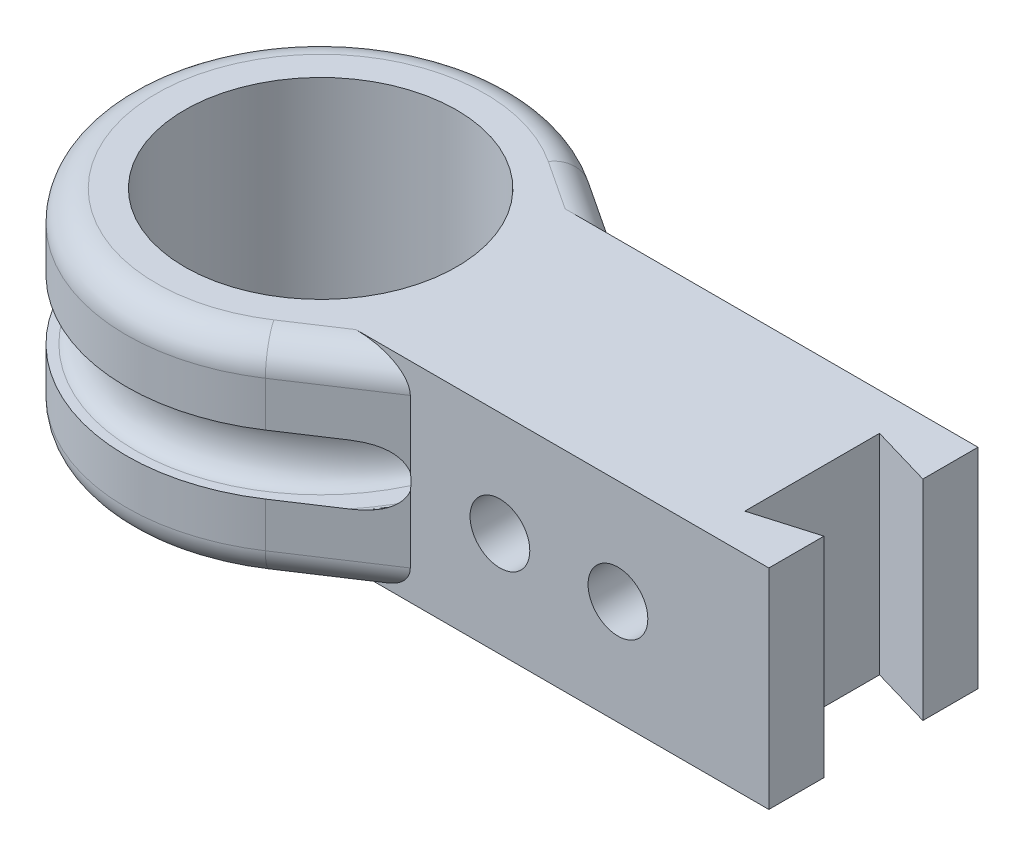
SolidWorks part; units mm, degrees
ref_plane "Front Plane" through (0, 0, 0) normal (0, 0, 1) x (1, 0, 0)
ref_plane "Top Plane" through (0, 0, 0) normal (0, 1, 0) x (1, 0, 0)
ref_plane "Right Plane" through (0, 0, 0) normal (1, 0, 0) x (0, 0, -1)
sketch "Sketch1" plane through (0, 0, 0) normal (0, 1, 0) x (1, 0, 0)
  line L0 (-10.3258, 0) -> (22.3498, 0) construction
  line L1 (6.5, 3.5) -> (3.578, 5.4266)
  line L2 (6.5, -3.5) -> (18.5, -3.5)
  line L4 (6.5, 3.5) -> (18.5, 3.5)
  line L5 (18.5, -3.5) -> (18.5, -1.655)
  line L6 (6.5, -3.5) -> (18.5, 3.5) construction
  line L7 (6.5, 3.5) -> (18.5, -3.5) construction
  line L8 (6.5, -3.5) -> (3.578, -5.4266)
  line L9 (18.5, 1.655) -> (16.45, 2.255)
  line L13 (16.45, -2.255) -> (16.45, 2.255)
  line L16 (16.45, -2.255) -> (18.5, -1.655)
  line L17 (18.5, 1.655) -> (18.5, 3.5)
  arc A0 (3.578, 5.4266) -> (3.578, -5.4266) centre (0, 0) ccw
  circle A1 centre (0, 0) radius 4.55
  point P5 (12.5, 0)
  point P11 (18.5, 0)
  point P18 (18.5, 1.655)
  point P19 (18.5, 2.255)
  point P23 (18.5, -1.655)
  dimension "D1" = 13
  dimension "D2" = 9.1
  dimension "D3" = 12
  dimension "D4" = 7
  dimension "D7" = 0.6
extrude "Boss-Extrude2" add sketch "Sketch1" along normal blind 7 contours A1 | L2 L5 L16 L13 L9 L17 L4 L1 A0 L8 region at (0, 0, 0)
sketch "Sketch2" plane through (0, 0, 0) normal (1, 0, 0) x (0, -1, 0)
  line L0 (0, -0.6001) -> (0, 7.5244) construction
  line L1 (-4.5, 6.805) -> (-4.5, 6.195)
  line L2 (-2.5, 6.195) -> (-2.5, 6.805)
  line L3 (-7.3353, 0) -> (0.2116, 0) construction
  line L4 (-7.3353, 6.5) -> (0.2116, 6.5) construction
  ellipse E0 centre (-3.5, 6.195) end of major axis (-4.5, 6.195) minor radius 0.6 (-4.5, 6.195) -> (-2.5, 6.195) ccw
  ellipse E1 centre (-3.5, 6.805) end of major axis (-4.5, 6.805) minor radius 0.6 (-4.5, 6.805) -> (-2.5, 6.805) cw
  point P5 (-4.5, 6.5)
  point P6 (-2.5, 6.5)
  point P20 (0, 6.5)
  dimension "D1" = 0.61
  dimension "D2" = 2
  dimension "D3" = 2.5
revolve "Cut-Revolve1" cut sketch "Sketch2" angle 360 about L3
sketch "Sketch3" plane through (0, 0, 3.5) normal (0, 0, 1) x (1, 0, 0)
  line L0 (18.5, 3.5) -> (6.0558, 3.5) construction
  line L1 (18.5, 7) -> (18.5, 0) construction
  line L2 (16.45, 7.1416) -> (16.45, -0.1293) construction
  circle A2 centre (13.45, 3.5) radius 1
  circle A3 centre (9.5, 3.5) radius 1
  point P4 (14.45, 3.5)
  point P5 (13.45, 3.5)
  point P11 (9.5, 3.5)
  point P13 (16.45, 3.5)
  dimension "D1" = 2
  dimension "D3" = 3.95
  dimension "D2" = 3
  dimension "D4" = 2.05
extrude "Cut-Extrude1" cut sketch "Sketch3" against normal up to next contours A3 | A2
fillet "Fillet4" radius 1 6 edges at (5.039, 0, -4.4633) (5.039, 0, 4.4633) (5.039, 7, -4.4633) (5.039, 7, 4.4633) (-6.5, 0, 0) (-6.5, 7, 0)
